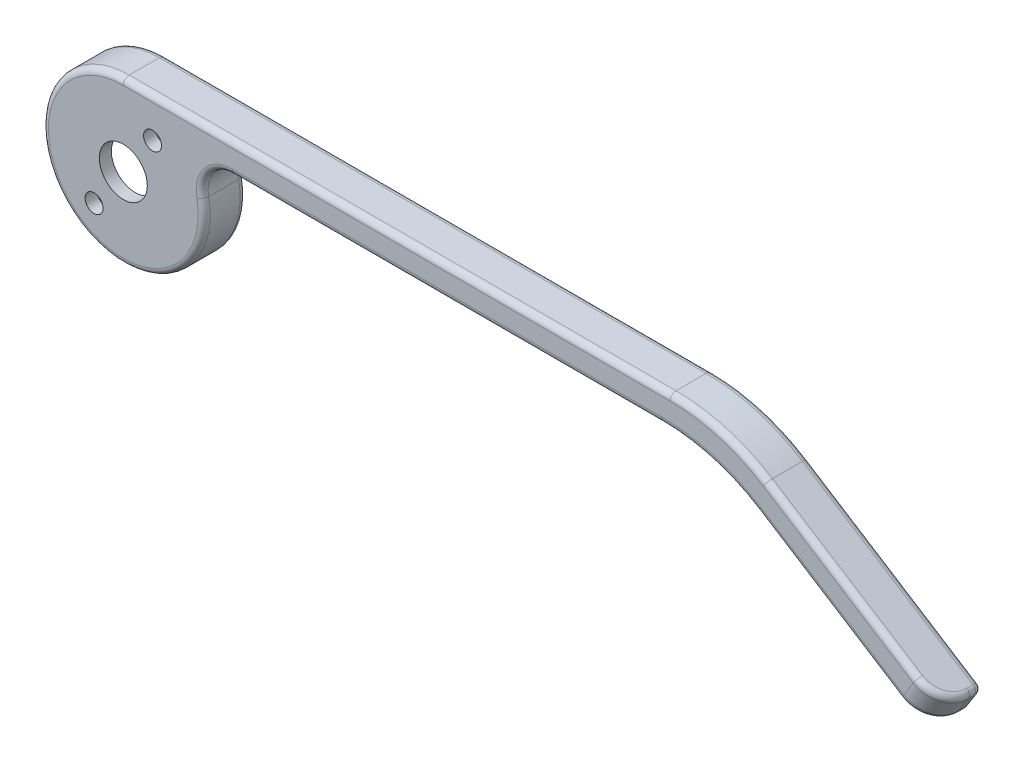
SolidWorks part; units mm, degrees
material "ABS"
ref_plane "Front" through (0, 0, 0) normal (0, 0, 1) x (1, 0, 0)
ref_plane "Top" through (0, 0, 0) normal (0, 1, 0) x (1, 0, 0)
ref_plane "Right" through (0, 0, 0) normal (1, 0, 0) x (0, 0, -1)
sketch "Esquisse1" plane through (0, 0, 0) normal (0, 0, 1) x (1, 0, 0)
  line L2 (0, 13.5) -> (100, 13.5)
  line L3 (10.4881, 8.5) -> (98.5463, 8.5)
  line L4 (100, 13.5) -> (136.6505, -9.7794)
  line L5 (136.6505, -9.7794) -> (133.9697, -14)
  line L6 (133.9697, -14) -> (98.5463, 8.5)
  arc A0 (0, 13.5) -> (10.4881, 8.5) centre (0, 0) ccw
  circle A1 centre (0, 0) radius 4
  dimension "D1" = 13.5
  dimension "D4" = 8
  dimension "D5" = 137
  dimension "D2" = 5
  dimension "D3" = 5
  dimension "D6" = 100
  dimension "D7" = 14
  dimension "D8" = 32.423
extrude "Boss.-Extru.1" add sketch "Esquisse1" along normal mid plane 7
fillet "Congé1" radius 5 2 edges at (10.4881, 8.5, 0) (135.3101, -11.8897, 3.5)
sketch "Esquisse5" plane through (0, 0, 3.5) normal (0, 0, 1) x (1, 0, 0)
  circle A0 centre (0, 0) radius 12.25
  circle A1 centre (0, 0) radius 4 construction
  dimension "D1" = 24.5
extrude "Enlèv. mat.-Extru.3" cut sketch "Esquisse5" against normal through all from offset 2 offset against normal yes
sketch "Esquisse6" plane through (0, 0, 3.5) normal (0, 0, 1) x (1, 0, 0)
  line L0 (-4.8754, -6.9628) -> (4.8754, 6.9628) construction
  line L2 (0, -50) -> (0, 50) construction
  circle A0 centre (4.8754, 6.9628) radius 1.5
  circle A1 centre (-4.8754, -6.9628) radius 1.5
  circle A2 centre (0, 0) radius 4 construction
  point P4 (0, 0)
  dimension "D1" = 3
  dimension "D2" = 17
  dimension "D3" = 35
extrude "Enlèv. mat.-Extru.4" cut sketch "Esquisse6" against normal through all
fillet "Congé3" radius 30 2 edges at (98.5463, 8.5, 0) (100, 13.5, 0)
fillet "Congé2" radius 1 21 edges at (45.6389, 13.5, 3.5) (53.995, 8.5, 3.5) (14.3104, 6.6836, 3.5) (45.6389, 13.5, -3.5) (53.995, 8.5, -3.5) (14.3104, 6.6836, -3.5) (-8.5956, -10.4098, 3.5) (-8.5956, -10.4098, -3.5) (119.8963, 0.8624, 3.5) (99.6532, 12.3072, 3.5) (117.829, -3.7479, 3.5) (98.1995, 7.3072, 3.5) (122.0065, -0.478, -3.5) (99.6532, 12.3072, -3.5) (119.9393, -5.0883, -3.5) (98.1995, 7.3072, -3.5) (133.9697, -14, -2.5) (136.6505, -9.7794, -2.5) (135.3101, -11.8897, -3.5) (135.4143, -8.9942, 2.0355) (132.7335, -13.2148, 2.0355)
sketch "Esquisse7" plane through (0, 0, 3.5) normal (0, 0, 1) x (1, 0, 0)
  circle A0 centre (0, 0) radius 12.1726
extrude "Boss.-Extru.2" [suppressed] add sketch "Esquisse7" against normal blind 0.2
